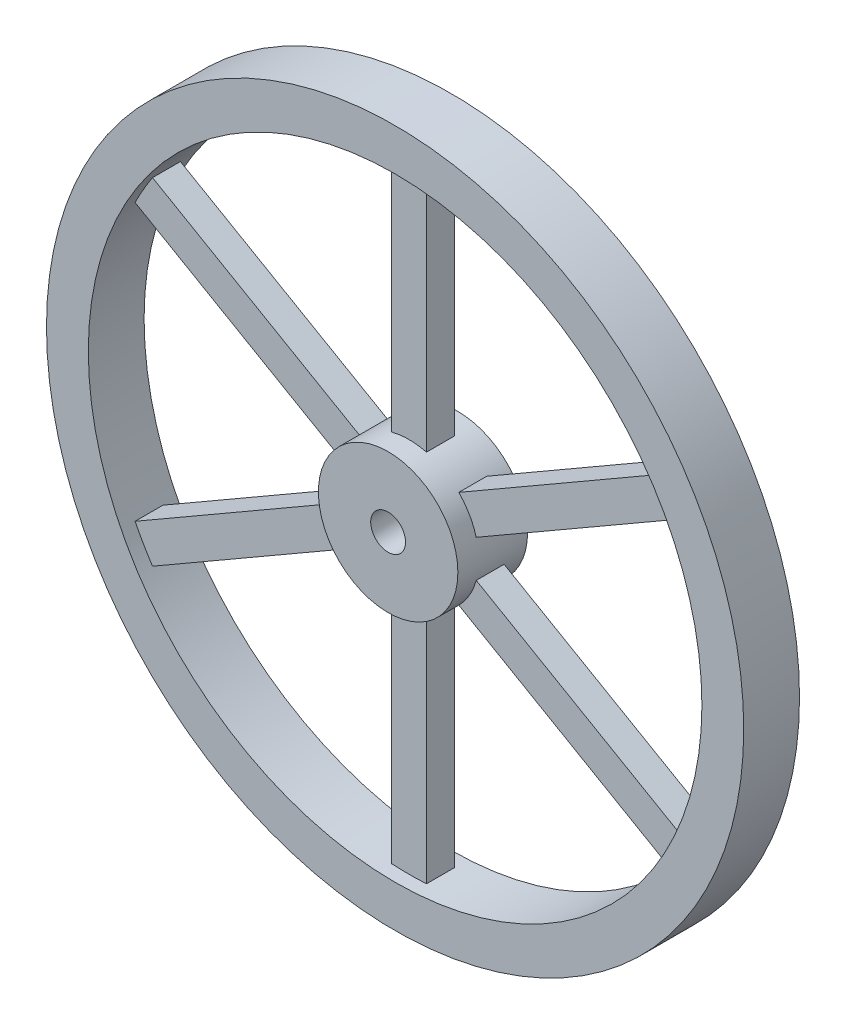
SolidWorks part; units mm, degrees
material "Gray Cast Iron"
ref_plane "Front Plane" through (0, 0, 0) normal (0, 0, 1) x (1, 0, 0)
ref_plane "Top Plane" through (0, 0, 0) normal (0, 1, 0) x (1, 0, 0)
ref_plane "Right Plane" through (0, 0, 0) normal (1, 0, 0) x (0, 0, -1)
sketch "Sketch1" plane through (0, 0, 0) normal (0, 0, 1) x (1, 0, 0)
  circle A0 centre (0, 0) radius 50
  circle A1 centre (0, 0) radius 44
  dimension "D1" = 100
  dimension "D2" = 88
extrude "Boss-Extrude1" add sketch "Sketch1" along normal mid plane 8
sketch "Sketch2" plane through (0, 0, 0) normal (0, 0, 1) x (1, 0, 0)
  circle A0 centre (0, 0) radius 10
  dimension "D1" = 20
extrude "Boss-Extrude2" add sketch "Sketch2" along normal mid plane 10
sketch "Sketch3" plane through (0, 0, 0) normal (0, 0, 1) x (1, 0, 0)
  line L0 (-2.5, 9) -> (2.5, 9)
  line L1 (2.5, 9) -> (2.5, 45)
  line L2 (2.5, 45) -> (-2.5, 45)
  line L3 (-2.5, 45) -> (-2.5, 9)
  dimension "D1" = 5
  dimension "D2" = 36
  dimension "D3" = 2.5
  dimension "D4" = 9
extrude "Boss-Extrude3" add sketch "Sketch3" along normal mid plane 4
sketch "Sketch4" plane through (0, 0, 0) normal (0, 0, 1) x (1, 0, 0)
  circle A0 centre (0, 0) radius 2.5
  dimension "D1" = 5
extrude "Cut-Extrude1" cut sketch "Sketch4" against normal mid plane 12
pattern_circular "CirPattern1" count 6 over 360 about axis through (0, 0, 5) along (0, 0, 1) of "Boss-Extrude3"
ref_axis "Axis1" through (0, 0, -5.5) along (0, 0, 1)
